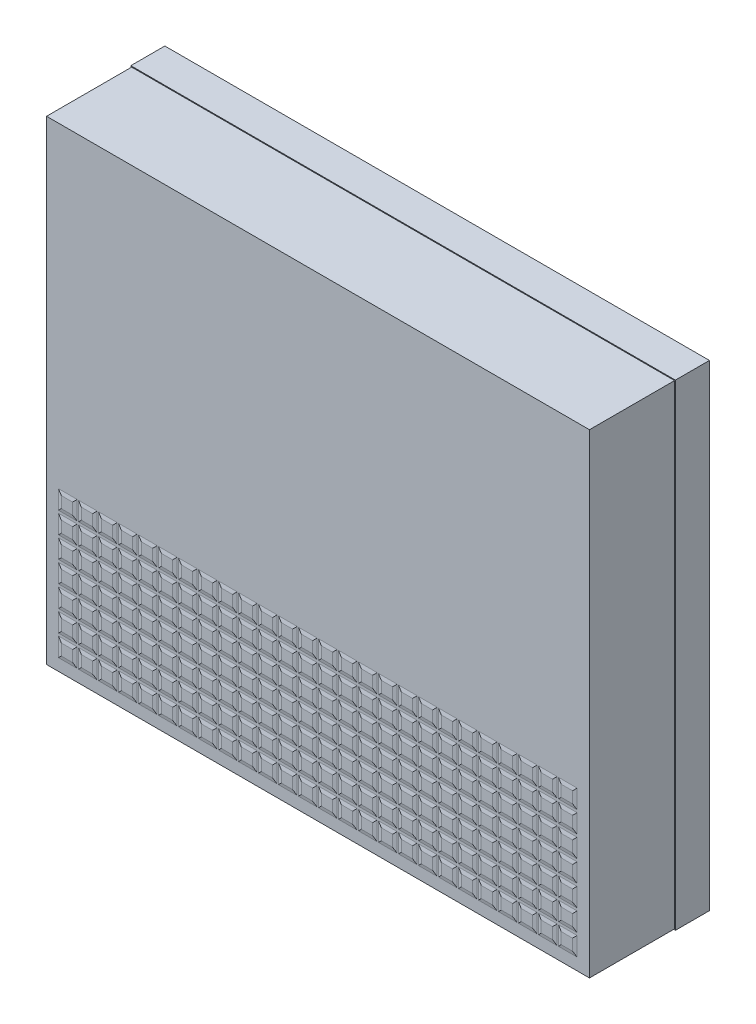
SolidWorks part; units mm, degrees
ref_plane "Alzado" through (0, 0, 0) normal (0, 0, 1) x (1, 0, 0)
ref_plane "Planta" through (0, 0, 0) normal (0, 1, 0) x (1, 0, 0)
ref_plane "Vista lateral" through (0, 0, 0) normal (1, 0, 0) x (0, 0, -1)
sketch "Croquis1" plane through (0, 0, 0) normal (0, 0, 1) x (1, 0, 0)
  line L1 (0, 0) -> (64, 0)
  line L2 (0, 0) -> (0, 56)
  line L3 (0, 56) -> (64, 56)
  line L4 (64, 0) -> (64, 56)
  dimension "D1" = 64
  dimension "D2" = 56
extrude "Saliente-Extruir1" add sketch "Croquis1" along normal blind 4
sketch "Croquis2" plane through (0, 0, 4) normal (0, 0, 1) x (1, 0, 0)
  line L0 (18.7802, 28.8194) -> (45.5958, 28.8194) construction
  text T0 "  mA" font "Arial Narrow" height in points 30
extrude "Saliente-Extruir2" add sketch "Croquis2" along normal blind 0.1
sketch "Croquis3" plane through (0, 0, 4) normal (0, 0, 1) x (1, 0, 0)
  line L0 (31.1882, 28.8194) -> (31.1882, 28.2143) construction
  line L1 (31.1882, 28.2143) -> (36.8918, 28.2143)
  line L2 (31.1882, 28.2143) -> (31.1882, 27.6143)
  line L3 (31.1882, 27.6143) -> (36.8918, 27.6143)
  line L4 (36.8918, 28.2143) -> (36.8918, 27.6143)
  line L5 (31.1882, 27.4143) -> (32.8882, 27.4143)
  line L6 (31.1882, 27.4143) -> (31.1882, 26.8143)
  line L7 (31.1882, 26.8143) -> (32.8882, 26.8143)
  line L8 (32.8882, 27.4143) -> (32.8882, 26.8143)
  line L9 (33.1882, 27.4143) -> (34.8882, 27.4143)
  line L10 (33.1882, 27.4143) -> (33.1882, 26.8143)
  line L11 (33.1882, 26.8143) -> (34.8882, 26.8143)
  line L12 (34.8882, 27.4143) -> (34.8882, 26.8143)
  line L13 (35.1882, 27.4143) -> (36.8882, 27.4143)
  line L14 (35.1882, 27.4143) -> (35.1882, 26.8143)
  line L15 (35.1882, 26.8143) -> (36.8882, 26.8143)
  line L16 (36.8882, 27.4143) -> (36.8882, 26.8143)
  line L17 (31.1882, 27.6143) -> (31.1882, 27.4143) construction
  dimension "D1" = 5.7037
  dimension "D2" = 0.6
  dimension "D3" = 0.2
  dimension "D4" = 0.6
  dimension "D5" = 0.6
  dimension "D6" = 0.2
  dimension "D7" = 0.2
  dimension "D8" = 0.6
  dimension "D9" = 1.7
  dimension "D10" = 0.3
  dimension "D11" = 0.3
  dimension "D12" = 1.7
  dimension "D13" = 1.7
extrude "Saliente-Extruir3" add sketch "Croquis3" along normal blind 0.1
sketch "Croquis4" plane through (0, 0, 4) normal (0, 0, 1) x (1, 0, 0)
  line L0 (9, 33) -> (55, 33) construction
  line L1 (64, 56) -> (0, 56) construction
  line L2 (0, 56) -> (0, 0) construction
  line L3 (64, 0) -> (64, 56) construction
  line L4 (9, 33) -> (8.6219, 33.3272)
  line L5 (55.3781, 33.3272) -> (55, 33)
  arc A0 (9, 33) -> (55, 33) centre (32, 13.092) cw
  arc A1 (8.6219, 33.3272) -> (55.3781, 33.3272) centre (32, 13.092) cw
  dimension "D1" = 23
  dimension "D2" = 9
  dimension "D3" = 9
  dimension "D4" = 0.5
extrude "Saliente-Extruir4" add sketch "Croquis4" along normal blind 0.1
sketch "Croquis5" plane through (0, 0, 4.1) normal (0, 0, 1) x (1, 0, 0)
  line L0 (8.6219, 33.3272) -> (5.9756, 35.6178)
  line L1 (9.019, 33.7771) -> (6.3683, 36.0715)
  line L2 (6.3683, 36.0715) -> (5.9756, 35.6178)
  arc A0 (55.3781, 33.3272) -> (8.6219, 33.3272) centre (32, 13.092) ccw construction
  arc A1 (8.6219, 33.3272) -> (9.019, 33.7771) centre (32, 13.092) cw
  dimension "D1" = 3.5
  dimension "D2" = 0.6
extrude "Saliente-Extruir5" add sketch "Croquis5" along normal blind 0.1 separate body
sketch "Croquis6" plane through (0, 0, 4.1) normal (0, 0, 1) x (1, 0, 0)
  line L0 (55.3781, 33.3272) -> (58.0244, 35.6178)
  line L1 (55.0073, 33.7478) -> (57.6575, 36.0417)
  line L2 (57.6575, 36.0417) -> (58.0244, 35.6178)
  line L3 (32, 44.0112) -> (32, 49.1138) construction
  line L4 (27.062, 43.6143) -> (26.503, 47.0694) construction
  line L5 (46.5619, 40.3674) -> (48.2103, 43.455) construction
  line L6 (36.938, 43.6143) -> (37.497, 47.0694) construction
  line L7 (37.7932, 47.0215) -> (37.2339, 43.565)
  line L8 (37.497, 47.0694) -> (37.7932, 47.0215)
  line L9 (17.4381, 40.3674) -> (15.7897, 43.455) construction
  line L10 (37.2009, 47.1173) -> (36.6417, 43.6608)
  line L11 (15.7897, 43.455) -> (16.0544, 43.5962)
  line L12 (16.0544, 43.5962) -> (17.7034, 40.5074)
  line L13 (15.7897, 43.455) -> (15.5251, 43.3137)
  line L14 (15.5251, 43.3137) -> (17.1741, 40.2248)
  line L15 (26.503, 47.0694) -> (26.7991, 47.1173)
  line L16 (37.497, 47.0694) -> (37.2009, 47.1173)
  line L17 (26.7991, 47.1173) -> (27.3583, 43.6608)
  line L18 (26.503, 47.0694) -> (26.2068, 47.0215)
  line L19 (26.2068, 47.0215) -> (26.7661, 43.565)
  line L20 (48.4749, 43.3137) -> (46.8259, 40.2248)
  line L21 (48.2103, 43.455) -> (48.4749, 43.3137)
  line L22 (47.9456, 43.5962) -> (46.2966, 40.5074)
  line L23 (48.2103, 43.455) -> (47.9456, 43.5962)
  arc A0 (55.3781, 33.3272) -> (8.6219, 33.3272) centre (32, 13.092) ccw construction
  arc A1 (55.3781, 33.3272) -> (55.0073, 33.7478) centre (32, 13.092) ccw
  arc A2 (55.3781, 33.3272) -> (8.6219, 33.3272) centre (32, 13.092) ccw construction
  arc A3 (17.7034, 40.5074) -> (17.1741, 40.2248) centre (32, 13.092) ccw
  arc A4 (27.3583, 43.6608) -> (26.7661, 43.565) centre (32, 13.092) ccw
  arc A5 (36.6417, 43.6608) -> (37.2339, 43.565) centre (32, 13.092) cw
  arc A6 (46.2966, 40.5074) -> (46.8259, 40.2248) centre (32, 13.092) cw
  dimension "D1" = 3.5
  dimension "D4" = 3.5
  dimension "D5" = 3.5
  dimension "D6" = 0.3
  dimension "D7" = 0.3
  dimension "D8" = 0.3
  dimension "D9" = 0.3
extrude "Saliente-Extruir6" add sketch "Croquis6" along normal blind 0.1 separate body
sketch "Croquis7" plane through (0, 0, 4) normal (0, 0, 1) x (1, 0, 0)
  line L0 (4.8361, 35.2106) -> (6.7983, 37.1728) construction
  text T0 "0"
extrude "Saliente-Extruir7" add sketch "Croquis7" along normal blind 0.1
sketch "Croquis8" plane through (0, 0, 4) normal (0, 0, 1) x (1, 0, 0)
  line L0 (12.8233, 42.3517) -> (17.5565, 45.0229) construction
  text T0 "10\r\n"
extrude "Saliente-Extruir8" add sketch "Croquis8" along normal blind 0.1
sketch "Croquis10" plane through (0, 0, 4) normal (0, 0, 1) x (1, 0, 0)
  line L0 (23.7059, 46.9719) -> (28.302, 47.863) construction
  text T0 "20"
extrude "Saliente-Extruir9" add sketch "Croquis10" along normal blind 0.1
sketch "Croquis11" plane through (0, 0, 4) normal (0, 0, 1) x (1, 0, 0)
  line L0 (35.0425, 47.8487) -> (39.8004, 47.0557) construction
  text T0 "30"
extrude "Saliente-Extruir10" add sketch "Croquis11" along normal blind 0.1
sketch "Croquis13" plane through (0, 0, 4) normal (0, 0, 1) x (1, 0, 0)
  line L0 (46.0528, 45.1665) -> (50.3468, 42.7618) construction
  text T0 "40\r\n"
extrude "Saliente-Extruir11" add sketch "Croquis13" along normal blind 0.1
sketch "Croquis14" plane through (0, 0, 4) normal (0, 0, 1) x (1, 0, 0)
  line L0 (56.6573, 38.0675) -> (59.054, 35.0835) construction
  text T0 "50\r\n"
extrude "Saliente-Extruir12" add sketch "Croquis14" along normal blind 0.1
sketch "Croquis15" plane through (0, 0, 4) normal (0, 0, 1) x (1, 0, 0)
  line L0 (32, 0) -> (32, 20.4942) construction
  line L1 (0, 0) -> (64, 0) construction
  circle A0 centre (32, 20.4942) radius 2.1186
extrude "Saliente-Extruir13" add sketch "Croquis15" along normal blind 0.2
sketch "Croquis16" plane through (0, 0, 4.2) normal (0, 0, 1) x (1, 0, 0)
  line L0 (32, 20.4942) -> (7.9998, 36.6599)
  line L1 (7.9457, 36.9375) -> (8.0016, 37.0205)
  line L2 (8.2792, 37.0746) -> (32.2793, 20.9089)
  line L3 (32.2793, 20.9089) -> (32, 20.4942)
  arc A0 (7.9998, 36.6599) -> (7.9457, 36.9375) centre (8.1116, 36.8258) cw
  arc A1 (8.0016, 37.0205) -> (8.2792, 37.0746) centre (8.1674, 36.9088) cw
  dimension "D2" = 0.2
  dimension "D1" = 0.5
extrude "Saliente-Extruir14" add sketch "Croquis16" along normal blind 0.1
sketch "Croquis17" plane through (0, 0, 4) normal (0, 0, 1) x (1, 0, 0)
  line L0 (64, 56) -> (0, 56) construction
  line L1 (0.1, 0.1) -> (63.9, 0.1)
  line L2 (0.1, 0.1) -> (0.1, 55.9)
  line L3 (0.1, 55.9) -> (63.9, 55.9)
  line L4 (63.9, 0.1) -> (63.9, 55.9)
  line L5 (0, 56) -> (0, 0) construction
  line L6 (64, 0) -> (64, 56) construction
  line L7 (0, 0) -> (64, 0) construction
  line L9 (1.5, 1.5) -> (62.5, 1.5)
  line L10 (1.5, 1.5) -> (1.5, 54.5)
  line L11 (1.5, 54.5) -> (62.5, 54.5)
  line L12 (62.5, 1.5) -> (62.5, 54.5)
  dimension "D1" = 0.1
  dimension "D2" = 0.1
  dimension "D3" = 0.1
  dimension "D4" = 0.1
  dimension "D5" = 1.4
  dimension "D6" = 1.4
  dimension "D7" = 1.4
  dimension "D8" = 1.4
extrude "Saliente-Extruir15" add sketch "Croquis17" along normal blind 10
sketch "Croquis19" plane through (0, 0, 14) normal (0, 0, 1) x (1, 0, 0)
  line L1 (1.5, 54.5) -> (62.5, 54.5)
  line L2 (1.5, 54.5) -> (1.5, 1.5)
  line L3 (1.5, 1.5) -> (62.5, 1.5)
  line L4 (62.5, 54.5) -> (62.5, 1.5)
extrude "Saliente-Extruir16" add sketch "Croquis19" against normal blind 1
sketch "Croquis20" plane through (0, 0, 14) normal (0, 0, 1) x (1, 0, 0)
  line L0 (1.5, 54.5) -> (1.5, 1.5) construction
  line L1 (1.5, 1.5) -> (3.7, 1.5)
  line L2 (1.5, 1.5) -> (1.5, 3.7)
  line L3 (1.5, 3.7) -> (3.7, 3.7)
  line L4 (3.7, 1.5) -> (3.7, 3.7)
  line L5 (1.5, 1.5) -> (62.5, 1.5) construction
  dimension "D1" = 2.2
  dimension "D2" = 2.2
extrude "Saliente-Extruir17" add sketch "Croquis20" along normal blind 0.1 draft 77
pattern_linear "MatrizL1" count 26 spacing 2.35 along (1, 0, 0) of "Saliente-Extruir17"
pattern_linear "MatrizL2" count 7 spacing 2.5 along (0, 1, 0) of "MatrizL1"
